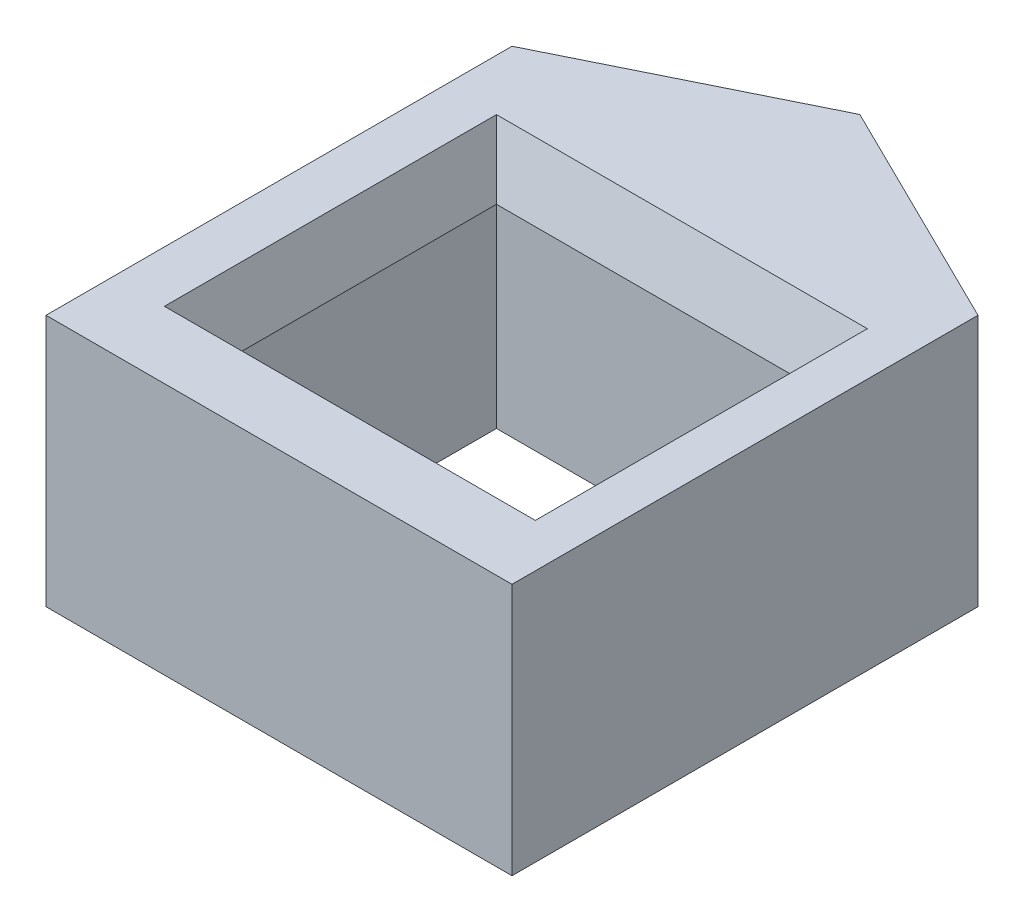
SolidWorks part; units mm, degrees
ref_plane "Front Plane" through (0, 0, 0) normal (0, 0, 1) x (1, 0, 0)
ref_plane "Top Plane" through (0, 0, 0) normal (0, 1, 0) x (1, 0, 0)
ref_plane "Right Plane" through (0, 0, 0) normal (1, 0, 0) x (0, 0, -1)
sketch "Sketch1" plane through (0, 0, 0) normal (0, 1, 0) x (1, 0, 0)
  line L0 (-6, 6) -> (0, 8.9564)
  line L1 (-4.175, 3.775) -> (4.375, 3.775)
  line L2 (-4.175, 3.775) -> (-4.175, -3.775)
  line L3 (-4.175, -3.775) -> (4.375, -3.775)
  line L4 (4.375, 3.775) -> (4.375, -3.775)
  line L6 (-6, 6) -> (-6, -6)
  line L7 (-6, -6) -> (6, -6)
  line L8 (6, 6) -> (6, -6)
  line L9 (0, 8.9564) -> (6, 6)
  point P11 (-4.175, 0)
  point P12 (-6, 0)
  dimension "D1" = 8.55
  dimension "D2" = 12
  dimension "D3" = 7.55
extrude "Boss-Extrude1" add sketch "Sketch1" along normal blind 6.5
chamfer "Chamfer1" distance 0.5 distance2 1.5 4 edges at (4.375, 6.5, 0) (0.1, 6.5, 3.775) (-4.175, 6.5, 0) (0.1, 6.5, -3.775) first distance on face at (0, 6.5, -1.7913)
